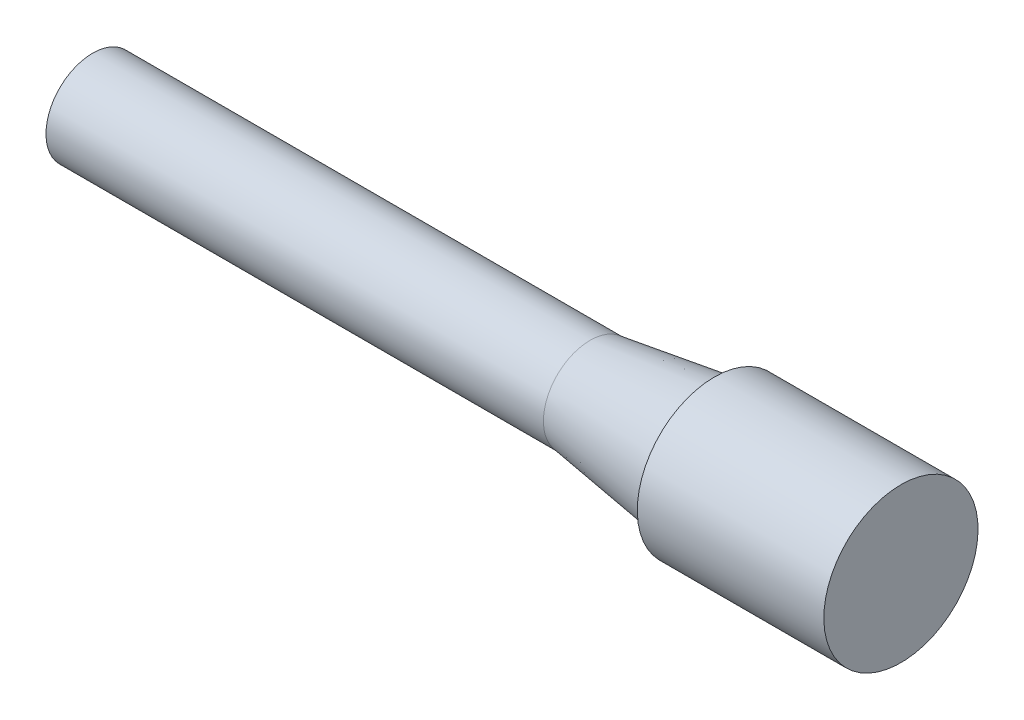
SolidWorks part; units mm, degrees
ref_plane "XY" through (0, 0, 0) normal (0, 0, 1) x (1, 0, 0)
ref_plane "XZ" through (0, 0, 0) normal (0, 1, 0) x (1, 0, 0)
ref_plane "YZ" through (0, 0, 0) normal (1, 0, 0) x (0, 0, -1)
ref_axis "X" through (-88.99, 0, 0) along (1, 0, 0)
ref_axis "Y" through (0, -55, 0) along (0, 1, 0)
ref_axis "Z" through (0, 0, 55) along (0, 0, -1)
sketch "Sketch1" plane through (0, 0, 0) normal (0, 0, 1) x (1, 0, 0)
  line L0 (0, 0) -> (-82.55, 0)
  line L2 (-31.75, 4.7625) -> (-19.05, 6.604)
  line L3 (-19.05, 6.604) -> (-19.05, 7.874)
  line L4 (-19.05, 7.874) -> (0, 7.874)
  line L5 (0, 7.874) -> (0, 0)
  line L6 (-82.55, 0) -> (-82.55, 4.7625)
  line L7 (-82.55, 4.7625) -> (-31.75, 4.7625)
  point P3 (-35.1869, 4.3064)
  dimension "D1" = 7.874
  dimension "D2" = 19.05
  dimension "D3" = 12.7
  dimension "D4" = 4.7625
  dimension "D5" = 1.27
  dimension "D6" = 50.8
revolve "Revolve1" add sketch "Sketch1" angle 360 about L0
